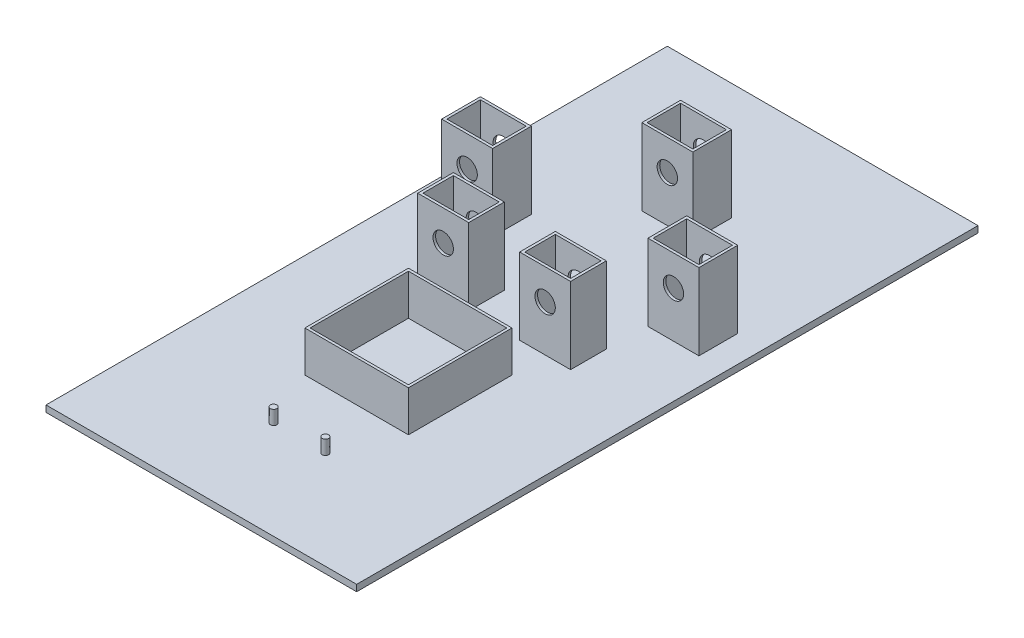
SolidWorks part; units mm, degrees
ref_plane "Front Plane" through (0, 0, 0) normal (0, 0, 1) x (1, 0, 0)
ref_plane "Top Plane" through (0, 0, 0) normal (0, 1, 0) x (1, 0, 0)
ref_plane "Right Plane" through (0, 0, 0) normal (1, 0, 0) x (0, 0, -1)
sketch "Sketch1" plane through (0, 0, 0) normal (0, 1, 0) x (1, 0, 0)
  line L1 (-152.4, -304.8) -> (152.4, -304.8)
  line L2 (-152.4, -304.8) -> (-152.4, 304.8)
  line L3 (-152.4, 304.8) -> (152.4, 304.8)
  line L4 (152.4, -304.8) -> (152.4, 304.8)
  line L5 (0, 304.8) -> (0, -304.8) construction
  line L6 (-152.4, 0) -> (152.4, 0) construction
  point P0 (0, 0)
  dimension "D1" = 609.6
  dimension "D2" = 304.8
extrude "Boss-Extrude1" add sketch "Sketch1" along normal blind 6.35
sketch "Sketch2" plane through (0, 6.35, 0) normal (0, 1, 0) x (1, 0, 0)
  line L1 (-25, 152.4) -> (25, 152.4)
  line L2 (-25, 152.4) -> (-25, 190.4)
  line L3 (-25, 190.4) -> (25, 190.4)
  line L4 (25, 152.4) -> (25, 190.4)
  line L5 (0, 190.4) -> (0, 152.4) construction
  line L6 (-25, 171.4) -> (25, 171.4) construction
  point P0 (0, 171.4)
  dimension "D1" = 50
  dimension "D2" = 38
  dimension "D3" = 152.4
extrude "Boss-Extrude2" add sketch "Sketch2" along normal blind 75
sketch "Sketch3" plane through (0, 0, -152.4) normal (0, 0, 1) x (1, 0, 0)
  line L0 (-25, 6.35) -> (25, 6.35) construction
  circle A0 centre (0, 51.35) radius 10
  dimension "D1" = 45
sketch "Sketch4" plane through (0, 6.35, 0) normal (0, 1, 0) x (1, 0, 0)
  line L1 (-76.2, 57.2) -> (-126.2, 57.2)
  line L2 (-76.2, 57.2) -> (-76.2, 95.2)
  line L3 (-76.2, 95.2) -> (-126.2, 95.2)
  line L4 (-126.2, 57.2) -> (-126.2, 95.2)
  line L5 (-101.2, 95.2) -> (-101.2, 57.2) construction
  line L6 (-76.2, 76.2) -> (-126.2, 76.2) construction
  point P0 (-101.2, 76.2)
  point P4 (0, 0)
  dimension "D1" = 50
  dimension "D2" = 38
  dimension "D3" = 76.2
  dimension "D4" = 76.2
extrude "Boss-Extrude3" add sketch "Sketch4" along normal blind 75
sketch "Sketch5" plane through (0, 6.35, 0) normal (0, 1, 0) x (1, 0, 0)
  line L0 (-25, 152.4) -> (25, 152.4) construction
  line L1 (-25, -17.5) -> (-75, -17.5)
  line L2 (-25, -17.5) -> (-25, 17.5)
  line L3 (-25, 17.5) -> (-75, 17.5)
  line L4 (-75, -17.5) -> (-75, 17.5)
  line L5 (-50, 17.5) -> (-50, -17.5) construction
  line L6 (-25, 0) -> (-75, 0) construction
  point P0 (-50, 0)
  point P6 (0, 152.4)
  dimension "D1" = 50
  dimension "D2" = 35
  dimension "D3" = 25
  dimension "D4" = 152.4
extrude "Boss-Extrude4" add sketch "Sketch5" along normal blind 75
mirror "Mirror1" about plane through (0, 0, 0) normal (1, 0, 0) of "Boss-Extrude3", "Boss-Extrude4"
shell "Shell11" thickness 2.54 removed face at (-101.2, 81.35, -76.2) removed face at (0, 81.35, -171.4) removed face at (-50, 81.35, 0) removed face at (50, 81.35, 0) removed face at (101.2, 81.35, -76.2)
extrude "Cut-Extrude2" cut sketch "Sketch3" against normal blind 75
sketch "Sketch6" plane through (0, 0, -57.2) normal (0, 0, 1) x (1, 0, 0)
  line L0 (-126.2, 6.35) -> (-76.2, 6.35) construction
  line L1 (-76.2, 81.35) -> (-76.2, 6.35) construction
  circle A0 centre (-101.2, 51.35) radius 10
  point P4 (-101.2, 6.35)
  dimension "D1" = 20
  dimension "D3" = 25
  dimension "D2" = 45
extrude "Cut-Extrude3" cut sketch "Sketch6" against normal blind 75
sketch "Sketch7" plane through (0, 0, 17.5) normal (0, 0, 1) x (1, 0, 0)
  line L0 (-75, 6.35) -> (-25, 6.35) construction
  circle A0 centre (-50, 51.35) radius 10
  dimension "D1" = 45
extrude "Cut-Extrude4" cut sketch "Sketch7" against normal blind 75
mirror "Mirror2" about plane through (0, 0, 0) normal (1, 0, 0) of "Cut-Extrude4", "Cut-Extrude3"
sketch "Sketch8" plane through (0, 6.35, 0) normal (0, 1, 0) x (1, 0, 0)
  line L1 (-50.8, -152.4) -> (50.8, -152.4)
  line L2 (-50.8, -152.4) -> (-50.8, -50.8)
  line L3 (-50.8, -50.8) -> (50.8, -50.8)
  line L4 (50.8, -152.4) -> (50.8, -50.8)
  line L5 (0, -50.8) -> (0, -152.4) construction
  line L6 (-50.8, -101.6) -> (50.8, -101.6) construction
  point P0 (0, -101.6)
  dimension "D1" = 101.6
  dimension "D2" = 101.6
  dimension "D3" = 0
  dimension "D4" = 152.4
extrude "Boss-Extrude5" add sketch "Sketch8" along normal blind 40
shell "Shell12" thickness 2.54 removed face at (0, 46.35, 101.6)
sketch "Sketch9" plane through (0, 6.35, 0) normal (0, 1, 0) x (1, 0, 0)
  circle A0 centre (-25.4, -208.4561) radius 3.16
  dimension "D1" = 6.32
  dimension "D2" = 25.4
extrude "Boss-Extrude6" add sketch "Sketch9" along normal blind 13.8176
mirror "Mirror3" about plane through (0, 0, 0) normal (1, 0, 0) of "Boss-Extrude6"
